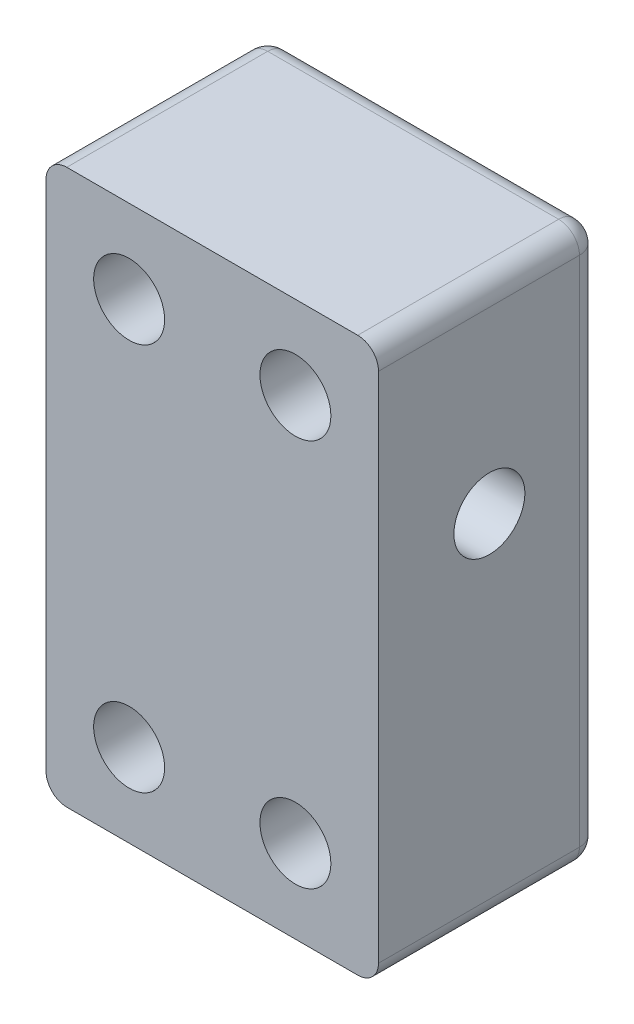
SolidWorks part; units mm, degrees
ref_plane "Front Plane" through (0, 0, 0) normal (0, 0, 1) x (1, 0, 0)
ref_plane "Top Plane" through (0, 0, 0) normal (0, 1, 0) x (1, 0, 0)
ref_plane "Right Plane" through (0, 0, 0) normal (1, 0, 0) x (0, 0, -1)
sketch "Sketch1" plane through (0, 0, 0) normal (0, 0, 1) x (1, 0, 0)
  line L0 (0, 26.9875) -> (19.05, 26.9875) construction
  line L1 (0, 0) -> (19.05, 0)
  line L2 (0, 0) -> (0, 31.75)
  line L3 (0, 31.75) -> (19.05, 31.75)
  line L4 (19.05, 0) -> (19.05, 31.75)
  circle A0 centre (4.7625, 26.9875) radius 2.032
  circle A1 centre (14.2875, 26.9875) radius 2.032
  circle A2 centre (4.7625, 4.7625) radius 2.032
  circle A3 centre (14.2875, 4.7625) radius 2.032
  point P14 (9.525, 31.75)
  point P16 (0, 0)
  point P17 (0, 0)
  point P18 (0, 0)
  point P19 (0, 0)
  dimension "D3" = 4.064
  dimension "D1" = 31.75
  dimension "D2" = 19.05
  dimension "D5" = 4.7625
  dimension "D6" = 4.7625
  dimension "D7" = 4.7625
  dimension "D4" = 4.7625
extrude "Boss-Extrude1" add sketch "Sketch1" along normal blind 12.7
sketch "Sketch2" plane through (0, 0, 0) normal (-1, 0, 0) x (0, 0, 1)
  line L1 (12.7, 31.75) -> (0, 31.75) construction
  line L2 (12.7, 31.75) -> (12.7, 0) construction
  circle A1 centre (6.35, 20.32) radius 2.032
  dimension "D2" = 6.35
  dimension "D3" = 4.064
  dimension "D1" = 11.43
extrude "Cut-Extrude1" cut sketch "Sketch2" against normal through all
fillet "Fillet1" radius 1.1906 8 edges at (9.525, 0, 0) (9.525, 31.75, 0) (19.05, 15.875, 0) (0, 15.875, 0) (0, 0, 6.35) (19.05, 0, 6.35) (0, 31.75, 6.35) (19.05, 31.75, 6.35)
equation "\"D4@Sketch1\"=\"D7@Sketch1\""
